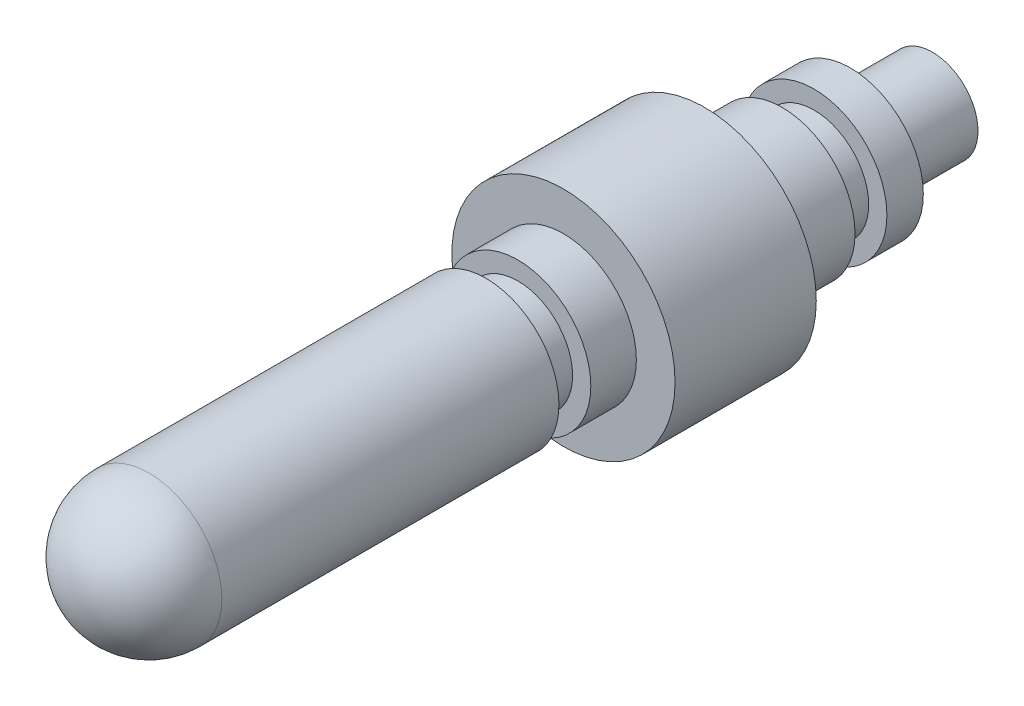
SolidWorks part; units mm, degrees
material "AISI 1020 Steel, Cold Rolled"
ref_plane "Front Plane" through (0, 0, 0) normal (0, 0, 1) x (1, 0, 0)
ref_plane "Top Plane" through (0, 0, 0) normal (0, 1, 0) x (1, 0, 0)
ref_plane "Right Plane" through (0, 0, 0) normal (1, 0, 0) x (0, 0, -1)
sketch "Sketch1" plane through (0, 0, 0) normal (0, 0, 1) x (1, 0, 0)
  circle A0 centre (0, 0) radius 1.27
  dimension "D1" = 2.54
extrude "Boss-Extrude1" add sketch "Sketch1" along normal blind 2.286
sketch "Sketch2" plane through (0, 0, 2.286) normal (0, 0, 1) x (1, 0, 0)
  circle A0 centre (0, 0) radius 2.032
  dimension "D1" = 4.064
extrude "Boss-Extrude2" add sketch "Sketch2" along normal blind 1.016
sketch "Sketch3" plane through (0, 0, 3.302) normal (0, 0, 1) x (1, 0, 0)
  circle A0 centre (0, 0) radius 1.524
  dimension "D1" = 3.048
extrude "Boss-Extrude3" add sketch "Sketch3" along normal blind 0.889
sketch "Sketch4" plane through (0, 0, 4.191) normal (0, 0, 1) x (1, 0, 0)
  circle A0 centre (0, 0) radius 2.032
  dimension "D1" = 4.064
extrude "Boss-Extrude4" add sketch "Sketch4" along normal blind 2.159
sketch "Sketch6" plane through (0, 0, 6.35) normal (0, 0, 1) x (1, 0, 0)
  circle A0 centre (0, 0) radius 3.1115
  dimension "D1" = 6.223
extrude "Boss-Extrude5" add sketch "Sketch6" along normal blind 3.937
sketch "Sketch7" plane through (0, 0, 10.287) normal (0, 0, 1) x (1, 0, 0)
  circle A0 centre (0, 0) radius 2.032
  dimension "D1" = 4.064
extrude "Boss-Extrude6" add sketch "Sketch7" along normal blind 1.27
sketch "Sketch8" plane through (0, 0, 11.557) normal (0, 0, 1) x (1, 0, 0)
  circle A0 centre (0, 0) radius 1.524
  dimension "D1" = 3.048
extrude "Boss-Extrude7" add sketch "Sketch8" along normal blind 0.889
sketch "Sketch9" plane through (0, 0, 12.446) normal (0, 0, 1) x (1, 0, 0)
  circle A0 centre (0, 0) radius 2.032
  dimension "D1" = 4.064
extrude "Boss-Extrude8" add sketch "Sketch9" along normal blind 11.43
fillet "Fillet1" radius 2.032 1 edges at (2.032, 0, 23.876) tangent propagation no
ref_axis "Axis1" through (0, 0, 4.191) along (0, 0, -1)
ref_axis "Axis2" through (0, 0, 12.446) along (0, 0, -1)
